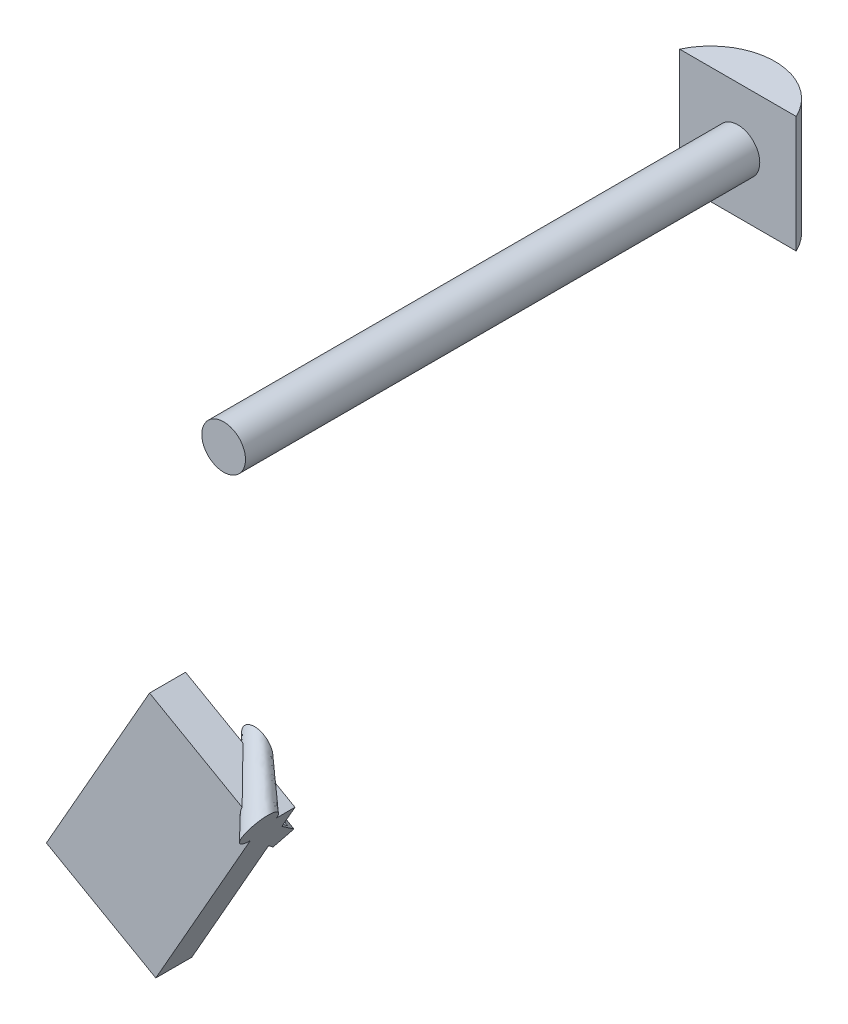
SolidWorks part; units mm, degrees
ref_plane "Front Plane" through (0, 0, 0) normal (0, 0, 1) x (1, 0, 0)
ref_plane "Top Plane" through (0, 0, 0) normal (0, 1, 0) x (1, 0, 0)
ref_plane "Right Plane" through (0, 0, 0) normal (1, 0, 0) x (0, 0, -1)
sketch "Sketch1" plane through (0, 0, 0) normal (0, 0, 1) x (1, 0, 0)
  circle A0 centre (0, 0) radius 2.3813
  dimension "D1" = 4.7625
extrude "Boss-Extrude1" add sketch "Sketch1" along normal blind 58.5966
sketch "Sketch2" plane through (0, 0, 0) normal (0, 1, 0) x (1, 0, 0)
  line L0 (0, -2.5637) -> (6.35, -2.5637)
  line L1 (6.35, -2.5637) -> (-6.35, -2.5637)
  arc A0 (-6.35, -2.5637) -> (6.35, -2.5637) centre (0, -5.5378) cw
  dimension "D1" = 6.35
  dimension "D2" = 12.7
extrude "Boss-Extrude2" add sketch "Sketch2" along normal mid plane 12.7 contours A0 L1 L0 region at (0, 0, 0.9006)
ref_plane "Plane1" through (2.07, -1.177, 0) normal (0.8693, -0.4943, 0) x (0, 0, -1)
ref_plane "Plane2" through (24.1501, -13.7321, 0) normal (0.8693, -0.4943, 0) x (0, 0, -1)
sketch "Sketch4" plane through (2.07, -1.177, 0) normal (0.8693, -0.4943, 0) x (0, 0, -1)
  circle A0 centre (-58.1131, 0) radius 1.9126
sketch "Sketch5" plane through (24.1501, -13.7321, 0) normal (0.8693, -0.4943, 0) x (0, 0, -1)
  circle A0 centre (-78.8962, 0) radius 1.9126
loft "Loft1" add profiles "Sketch5", "Sketch4" connector at (24.6354, -12.8786, 80.5375) connector at (2.7676, 0.0498, 56.8224)
ref_point "Point1"
sketch "Sketch8" plane through (24.1501, -13.7321, 0) normal (0.8693, -0.4943, 0) x (0, 0, -1)
  line L0 (-78.7583, -2.0505) -> (-73.9822, -6.8266)
  line L1 (-78.8962, 0) -> (-76.922, 0)
  line L2 (-78.8962, 0) -> (-78.8962, -2.0505)
  line L3 (-78.8962, -2.0505) -> (-78.7583, -2.0505)
  line L4 (-76.922, 0) -> (-76.922, -1.0253)
  line L5 (-73.9822, -6.8266) -> (-72.4644, -5.3088)
  line L6 (-72.4644, -5.3088) -> (-76.922, -1.0253)
extrude "Boss-Extrude4" add sketch "Sketch8" against normal blind 2.032
sketch "Sketch9" plane through (24.1501, -13.7321, 0) normal (0.8693, -0.4943, 0) x (0, 0, -1)
  line L1 (-78.8962, 0) -> (-74.9724, 0)
  line L2 (-78.8962, 0) -> (-78.8962, -22.7414)
  line L3 (-78.8962, -22.7414) -> (-74.9724, -22.7414)
  line L4 (-74.9724, 0) -> (-74.9724, -22.7414)
extrude "Boss-Extrude5" add sketch "Sketch9" against normal blind 13.716
sketch "Sketch10" plane through (2.07, -1.177, 0) normal (0.8693, -0.4943, 0) x (0, 0, -1)
  line L1 (-73.9934, 12.3542) -> (-43.0376, 12.3542)
  line L2 (-73.9934, 12.3542) -> (-73.9934, -4.4398)
  line L3 (-73.9934, -4.4398) -> (-43.0376, -4.4398)
  line L4 (-43.0376, 12.3542) -> (-43.0376, -4.4398)
  point P4 (-72.9468, 11.9726)
  point P5 (-73.9934, 12.3542)
extrude "Cut-Extrude1" cut sketch "Sketch10" along normal blind 25.146
